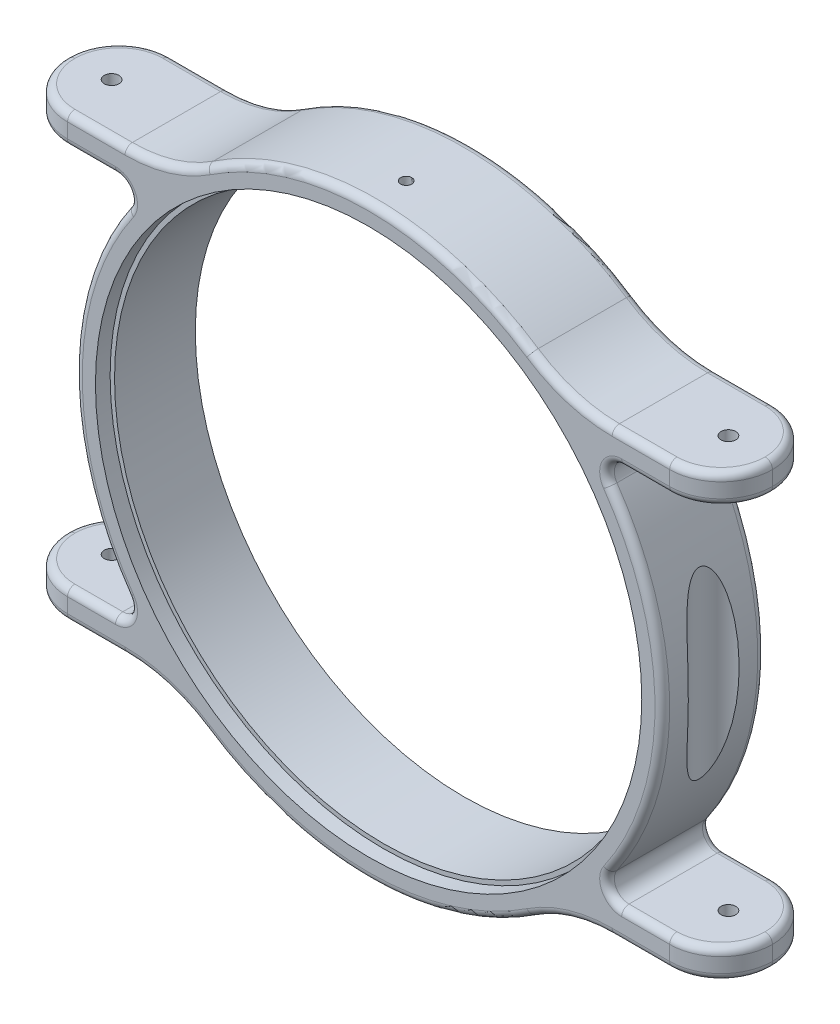
SolidWorks part; units mm, degrees
ref_plane "Front Plane" through (0, 0, 0) normal (0, 0, 1) x (1, 0, 0)
ref_plane "Top Plane" through (0, 0, 0) normal (0, 1, 0) x (1, 0, 0)
ref_plane "Right Plane" through (0, 0, 0) normal (1, 0, 0) x (0, 0, -1)
sketch "Sketch1" plane through (0, 0, 0) normal (0, 0, -1) x (-1, 0, 0)
  circle A0 centre (0, 0) radius 18.3 construction
  circle A1 centre (0, 0) radius 18.3
  circle A2 centre (0, 0) radius 20 construction
  circle A3 centre (0, 0) radius 20
extrude "Boss-Extrude1" add sketch "Sketch1" against normal blind 5 and the other way blind 2
sketch "Sketch2" plane through (0, 0, -2) normal (0, 0, -1) x (-1, 0, 0)
  circle A0 centre (0, 0) radius 19.3
  circle A1 centre (0, 0) radius 18.3 construction
  dimension "D1" = 1
extrude "Cut-Extrude1" cut sketch "Sketch2" against normal blind 0.5
sketch "Sketch5" plane through (-1.3502, 4.2289, -2.1606) normal (0, 1, 0) x (1, 0, 0)
  spline S4 degree 5 poles (1.3502, -4.9828) (1.4703, -4.9828) (1.5905, -4.9358) (1.6854, -4.8407) (1.7794, -4.6006) (1.6854, -4.3604) (1.5905, -4.2653) (1.4703, -4.2183) (1.3502, -4.2183) knots 4.92139 4.92139 4.92139 4.92139 4.92139 4.92139 7.382085 7.382085 7.382085 9.842779 9.842779 9.842779 9.842779 9.842779 9.842779
  spline S5 degree 5 poles (1.3502, -4.2183) (1.2301, -4.2183) (1.1099, -4.2653) (1.015, -4.3604) (0.9209, -4.6006) (1.015, -4.8407) (1.1099, -4.9358) (1.2301, -4.9828) (1.3502, -4.9828) knots 0 0 0 0 0 0 2.460695 2.460695 2.460695 4.92139 4.92139 4.92139 4.92139 4.92139 4.92139
extrude "Cut-Extrude9" cut sketch "Sketch5" along normal through all
sketch "Sketch6" plane through (0, 0, 0) normal (0, 0, 1) x (1, 0, 0)
  line L0 (13.2288, 15) -> (24, 15)
  line L1 (-24, 15) -> (-13.2288, 15)
  line L2 (-24, 15) -> (-24, -15)
  line L3 (-24, -15) -> (-13.2288, -15)
  line L4 (24, 15) -> (24, -15)
  line L5 (13.2288, -15) -> (24, -15)
  circle A0 centre (0, 0) radius 20 construction
  circle A1 centre (0, 0) radius 20
  dimension "D1" = 30
  dimension "D2" = 15
  dimension "D3" = 24
  dimension "D4" = 24
extrude "Boss-Extrude2" add sketch "Sketch6" along normal up to surface and the other way up to surface contours A1 L1 L2 L3 | A1 L5 L4 L0 region at (20.6478, 0, 0) region at (-20.6478, 0, 0) up to face at (-18.3, 0, 5) other way up to face at (-19.3, 0, -2)
fillet "Fillet4" radius 10 4 edges at (13.2288, -15, 1.5) (13.2288, 15, 1.5) (-13.2288, -15, 1.5) (-13.2288, 15, 1.5)
sketch "Sketch9" plane through (0, 0, 0) normal (0, 0, 1) x (1, 0, 0)
  line L11 (-16.5831, 13) -> (-24, 13)
  line L12 (-15.1987, 13) -> (-24, 13)
  line L14 (24, 13) -> (16.5831, 13)
  line L15 (24, 13) -> (15.1987, 13)
  line L17 (-16.5831, -13) -> (-24, -13)
  line L18 (-15.1987, -13) -> (-24, -13)
  line L19 (-24, 13) -> (-24, -13)
  line L20 (24, -13) -> (16.5831, -13)
  line L21 (24, -13) -> (15.1987, -13)
  line L22 (24, 13) -> (24, -13)
  arc A3 (-15.1987, 13) -> (-15.1987, -13) centre (0, 0) ccw
  arc A4 (15.1987, -13) -> (15.1987, 13) centre (0, 0) ccw
  arc A15 (-16.5831, 13) -> (-9.9499, 15) centre (-16.5831, 25) ccw
  dimension "D3" = 2
  dimension "D4" = 2
  dimension "D5" = 2
  dimension "D6" = 2
extrude "Cut-Extrude12" cut sketch "Sketch9" against normal through all and the other way through all contours L21 L22 L15 | L12 L19 L18 region at (-21.0647, 0, 0) region at (21.0647, 0, 0)
fillet "Fillet5" radius 1 4 edges at (15.1987, 13, 1.5) (15.1987, -13, 1.5) (-15.1987, -13, 1.5) (-15.1987, 13, 1.5)
fillet "Fillet6" radius 3.5 8 edges at (-24, 14, 5) (-24, 14, -2) (-24, -14, 5) (-24, -14, -2) (24, -14, 5) (24, -14, -2) (24, 14, 5) (24, 14, -2)
fillet "Fillet7" radius 0.5 56 edges at (-18.8668, 13, -2) (-22.9749, 13, -0.9749) (-22.9749, 13, 3.9749) (-18.8668, 13, 5) (-18.8668, -13, 5) (-22.9749, -13, 3.9749) (-22.9749, -13, -0.9749) (-18.8668, -13, -2) (18.5416, -15, -2) (22.9749, -15, -0.9749) (22.9749, -15, 3.9749) (18.5416, -15, 5) (13.6964, -15.4257, 5) (0, -20, 5) (-13.6964, -15.4257, 5) (-18.5416, -15, 5) (-22.9749, -15, 3.9749) (-22.9749, -15, -0.9749) (-18.5416, -15, -2) (-13.6964, -15.4257, -2) (0, -20, -2) (18.8668, -13, -2) (22.9749, -13, -0.9749) (22.9749, -13, 3.9749) (18.8668, -13, 5) (18.8668, 13, 5) (22.9749, 13, 3.9749) (22.9749, 13, -0.9749) (18.8668, 13, -2) (-13.6964, 15.4257, -2) (-18.5416, 15, -2) (-22.9749, 15, -0.9749) (-22.9749, 15, 3.9749) (-18.5416, 15, 5) (-13.6964, 15.4257, 5) (0, 20, 5) (13.6964, 15.4257, 5) (18.5416, 15, 5) (22.9749, 15, 3.9749) (22.9749, 15, -0.9749) (18.5416, 15, -2) (13.6964, 15.4257, -2) (13.6964, -15.4257, -2) (0, 20, -2) (16.3473, -12.4629, -2) (16.3473, -12.4629, 5) (20, 0, 5) (16.3473, 12.4629, 5) (16.3473, 12.4629, -2) (-16.3473, 12.4629, -2) (-16.3473, 12.4629, 5) (-20, 0, 5) (-16.3473, -12.4629, 5) (-16.3473, -12.4629, -2) (20, 0, -2) (-20, 0, -2)
sketch "Sketch10" plane through (0, 0, 0) normal (0, 1, 0) x (1, 0, 0)
  circle A0 centre (-21, -1.5) radius 0.5
  circle A1 centre (21, -1.5) radius 0.5
  dimension "D1" = 1
  dimension "D2" = 21
  dimension "D3" = 21
  dimension "D4" = 1.5
extrude "Cut-Extrude13" cut sketch "Sketch10" against normal through all and the other way through all
sketch "Sketch11" plane through (0, 0, 5) normal (0, 0, 1) x (1, 0, 0)
  circle A2 centre (0, 0) radius 18.6
  circle A3 centre (0, 0) radius 18.6
  dimension "D1" = 0.3
extrude "Cut-Extrude14" cut sketch "Sketch11" against normal blind 1
sketch "Sketch13" plane through (0, 13, 0) normal (0, -1, 0) x (1, 0, 0)
  circle A0 centre (21, 1.5) radius 2
  circle A1 centre (-21, 1.5) radius 2
  dimension "D1" = 4
extrude "Cut-Extrude16" cut sketch "Sketch13" along normal up to surface (26 mm away) up to face at (20.5, -13, 1.5)
